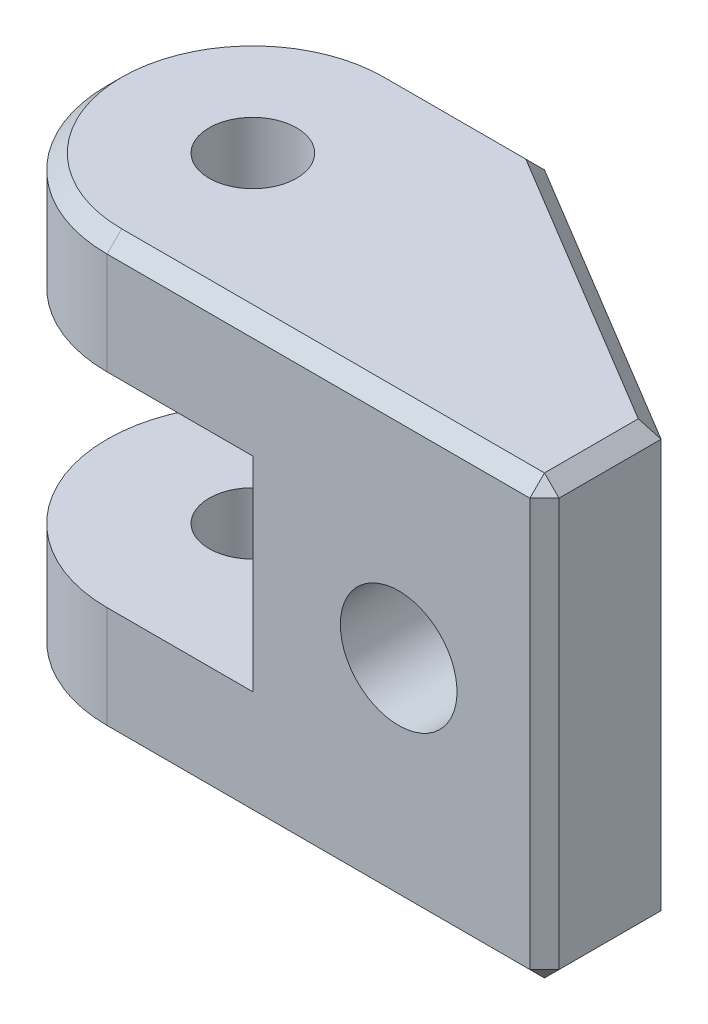
SolidWorks part; units mm, degrees
material "5052-O"
ref_plane "正面" through (0, 0, 0) normal (0, 0, 1) x (1, 0, 0)
ref_plane "平面" through (0, 0, 0) normal (0, 1, 0) x (1, 0, 0)
ref_plane "右側面" through (0, 0, 0) normal (1, 0, 0) x (0, 0, -1)
sketch "ｽｹｯﾁ1" plane through (0, 0, 0) normal (0, 1, 0) x (1, 0, 0)
  line L0 (0, 0) -> (20, 0)
  line L1 (20, 0) -> (20, 4)
  line L2 (0, 0) -> (0, 10)
  line L3 (0, 10) -> (10, 10)
  line L4 (10, 10) -> (20, 4)
extrude "ﾎﾞｽ - 押し出し1" add sketch "ｽｹｯﾁ1" along normal blind 15
sketch "ｽｹｯﾁ2" plane through (0, 0, -10) normal (0, 0, -1) x (-1, 0, 0)
  line L0 (-10, 15) -> (-10, 11)
  line L1 (-10, 15) -> (-10, 0) construction
  line L2 (-10, 11) -> (0, 11)
  line L3 (0, 15) -> (0, 0) construction
  line L4 (0, 11) -> (0, 4)
  line L5 (0, 4) -> (-10, 4)
  line L6 (-10, 4) -> (-10, 11)
  line M2 (0, 0) -> (0, 15)
  line M4 (-10, 15) -> (-10, 0)
extrude "ｶｯﾄ - 押し出し1" cut sketch "ｽｹｯﾁ2" against normal through all contours L5 L2 M2 M4 region at (5, 7.5, -10)
sketch "ｽｹｯﾁ3" plane through (10, 0, 0) normal (-1, 0, 0) x (0, 0, 1)
  line L0 (0, 11) -> (-4, 11)
  line L1 (0, 11) -> (-10, 11) construction
  line L2 (-4, 11) -> (-4, 4)
  line L3 (-4, 4) -> (-10, 4)
  line L4 (-10, 4) -> (-10, 11)
  line L5 (-10, 11) -> (-4, 11)
  line M1 (-10, 11) -> (-10, 4)
  line M2 (-10, 4) -> (0, 4)
  line M4 (0, 11) -> (-10, 11)
extrude "ｶｯﾄ - 押し出し2" cut sketch "ｽｹｯﾁ3" against normal through all contours L2 M4 M1 M2 region at (10, 7.5, -7)
sketch "ｽｹｯﾁ4" plane through (0, 0, -4) normal (0, 0, -1) x (-1, 0, 0)
  circle A0 centre (-15, 7.5) radius 2
extrude "ｶｯﾄ - 押し出し3" cut sketch "ｽｹｯﾁ4" against normal through all
fillet "ﾌｨﾚｯﾄ1" radius 5 4 edges at (0, 2, 0) (0, 2, -10) (0, 13, 0) (0, 13, -10)
sketch "ｽｹｯﾁ5" plane through (0, 0, 0) normal (0, -1, 0) x (1, 0, 0)
  circle A0 centre (5, -5) radius 1.5
extrude "ｶｯﾄ - 押し出し4" cut sketch "ｽｹｯﾁ5" against normal through all
chamfer "面取り1" distance 0.5 angle 45 13 edges at (20, 0, -2) (15, 0, -7) (7.5, 0, -10) (1.4645, 0, -8.5355) (1.4645, 0, -1.4645) (12.5, 0, 0) (20, 7.5, 0) (20, 15, -2) (12.5, 15, 0) (1.4645, 15, -1.4645) (1.4645, 15, -8.5355) (7.5, 15, -10) (15, 15, -7)
